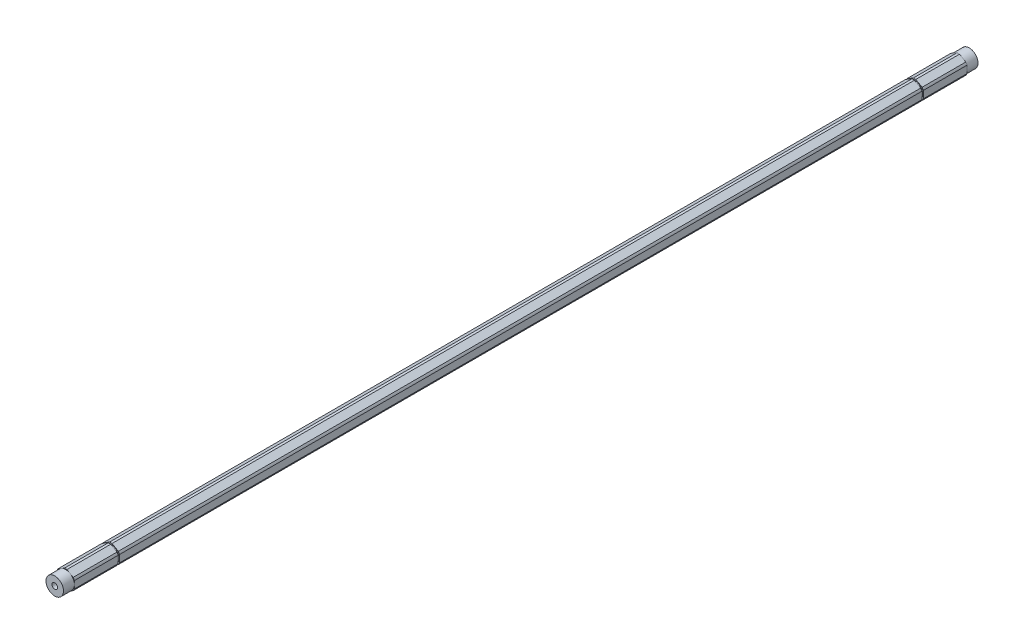
SolidWorks part; units mm, degrees
material "7075-T6 (SN)"
ref_plane "Front Plane" through (0, 0, 0) normal (0, 0, 1) x (1, 0, 0)
ref_plane "Top Plane" through (0, 0, 0) normal (0, 1, 0) x (1, 0, 0)
ref_plane "Right Plane" through (0, 0, 0) normal (1, 0, 0) x (0, 0, -1)
sketch "Sketch1" plane through (0, 0, 0) normal (0, 0, 1) x (1, 0, 0)
  line L1 (0, 7.3323) -> (-6.35, 3.6662)
  line L2 (-6.35, 3.6662) -> (-6.35, -3.6662)
  line L3 (-6.35, -3.6662) -> (0, -7.3323)
  line L4 (0, -7.3323) -> (6.35, -3.6662)
  line L5 (6.35, -3.6662) -> (6.35, 3.6662)
  line L6 (6.35, 3.6662) -> (0, 7.3323)
  circle A0 centre (0, 0) radius 6.35 construction
  circle A1 centre (0, 0) radius 2.0193
  circle A2 centre (0, 0) radius 6.875
  dimension "D1" = 12.7
  dimension "D2" = 4.0386
  dimension "D3" = 13.75
extrude "Boss-Extrude1" add sketch "Sketch1" along normal mid plane 663.575 contours L5 A2 L6 L1 L2 L3 L4 A1 region at (0, 6.6878, 0)
sketch "Sketch2" plane through (0, 0, -331.7875) normal (0, 0, -1) x (-1, 0, 0)
  circle A0 centre (0, 0) radius 6.35
  dimension "D1" = 12.7
extrude "Cut-Extrude-Thin1" cut sketch "Sketch2" against normal blind 7.9375 thin thin type one direction wall 2.54
sketch "Sketch3" plane through (0, 0, 0) normal (0, 1, 0) x (1, 0, 0)
  line L1 (8.6172, 292.1) -> (5.9436, 292.1)
  line L2 (8.6172, 292.1) -> (8.6172, 291.1094)
  line L3 (8.6172, 291.1094) -> (5.9436, 291.1094)
  line L4 (5.9436, 292.1) -> (5.9436, 291.1094)
  line L9 (6.35, 331.7875) -> (-6.35, 331.7875) construction
  line L11 (0, -331.7875) -> (0, 323.85) construction
  point P4 (8.6172, 292.1)
  point P7 (0, 291.2628)
  point P11 (0, 326.1054)
  point P12 (5.1516, 330.2)
  point P14 (2.1635, 319.6425)
  point P17 (1.6946, 290.4285)
  dimension "D1" = 0.9906
  dimension "D2" = 39.6875
  dimension "D3" = 5.9436
revolve "Cut-Revolve4" cut sketch "Sketch3" angle 360 about axis through (0, 0, -323.85) along (0, 0, -1)
mirror "Mirror1" about plane through (0, 0, 0) normal (0, 0, 1) of "Cut-Revolve4", "Cut-Extrude-Thin1"
hole_wizard "#10-32 Tapped Hole1" positions "3DSketch1" profile "Sketch4" tap size "#10-32" standard "ANSI Inch"
sketch3d "3DSketch1"
  circle A0 centre (0, 0, 331.7875) radius 2.0193 construction
  circle A1 centre (0, 0, -331.7875) radius 2.0193 construction
  point P0 (0, 0, -331.7875)
  point P2 (0, 0, 331.7875)
  point P8 (0, 0, 333.8068)
  point P12 (0, 0, -329.7682)
sketch "Sketch4" plane through (0, 0, -331.7875) normal (1, 0, 0) x (0, 1, 0)
  line L0 (0, 0) -> (0, 13.2428)
  line L1 (0, 13.2428) -> (2.0193, 12.0294)
  line L2 (2.0193, 12.0294) -> (2.0193, 0)
  line L5 (2.0193, 0) -> (0, 0)
  line L10 (0, 13.2428) -> (-2.0193, 12.0294) construction
  line L11 (0, -6.35) -> (0, 107.95) construction
  dimension "Tap Drill Dia." = 4.0386
  dimension "Tap Drill Depth" = 12.0294
  dimension "Drill Angle" = 118
cosmetic thread "Hole Thread1" parameters "D1"=9.652, "D2"=4.826
cosmetic thread "Hole Thread2" parameters "D1"=9.652, "D2"=4.826
equation "\"D3@Sketch1\"=13.75mm"
